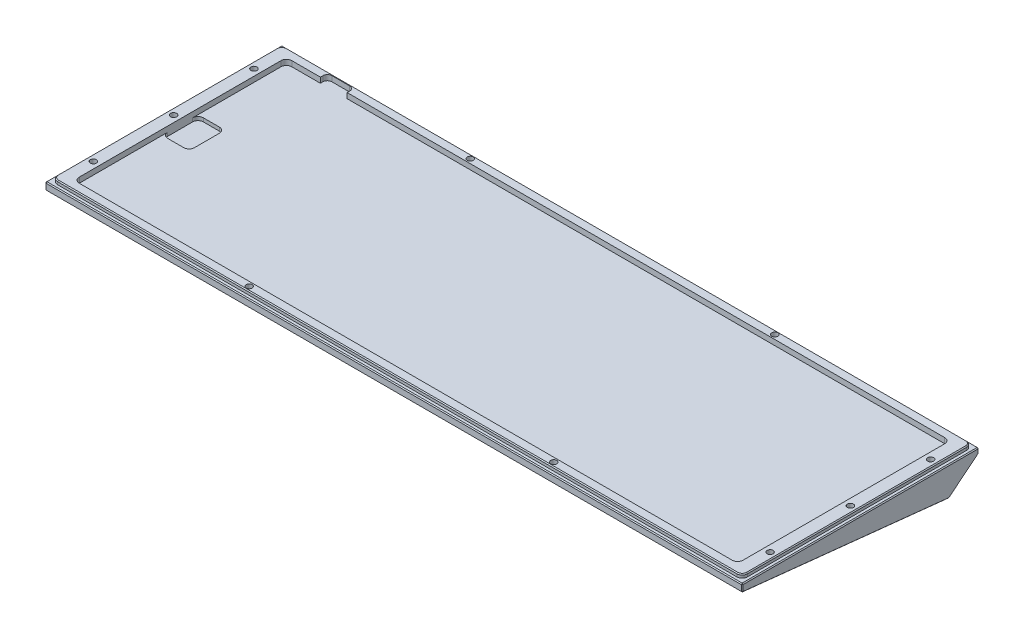
SolidWorks part; units mm, degrees
material "6061-T6 (SS)"
ref_plane "Front Plane" through (0, 0, 0) normal (0, 0, 1) x (1, 0, 0)
ref_plane "Top Plane" through (0, 0, 0) normal (0, 1, 0) x (1, 0, 0)
ref_plane "Right Plane" through (0, 0, 0) normal (1, 0, 0) x (0, 0, -1)
sketch "Sketch1" plane through (0, 0, 0) normal (0, 1, 0) x (1, 0, 0)
  line L1 (0, 0) -> (390.7, 0)
  line L2 (0, 0) -> (0, 132.7)
  line L3 (0, 132.7) -> (390.7, 132.7)
  line L4 (390.7, 0) -> (390.7, 132.7)
  dimension "D1" = 390.7
  dimension "D2" = 132.7
extrude "MainBody" add sketch "Sketch1" along normal blind 18.5
sketch "Sketch2" plane through (0, 18.5, 0) normal (0, 1, 0) x (1, 0, 0)
  line L0 (390.7, 132.7) -> (0, 132.7) construction
  line L1 (2, 130.7) -> (388.7, 130.7)
  line L2 (2, 130.7) -> (2, 2)
  line L3 (2, 2) -> (388.7, 2)
  line L4 (388.7, 130.7) -> (388.7, 2)
  line L5 (0, 132.7) -> (0, 0) construction
  line L7 (0, 132.7) -> (390.7, 132.7)
  line L8 (0, 132.7) -> (0, 0)
  line L9 (0, 0) -> (390.7, 0)
  line L10 (390.7, 132.7) -> (390.7, 0)
  point P4 (195.35, 130.7)
  point P7 (195.35, 132.7)
  point P8 (2, 66.35)
  point P11 (0, 66.35)
  line M5 (0, 132.7) -> (0, 0)
  line M6 (0, 0) -> (390.7, 0)
  line M7 (390.7, 0) -> (390.7, 132.7)
  line M8 (390.7, 132.7) -> (0, 132.7)
  dimension "D1" = 2
  dimension "D2" = 2
extrude "AligmentLip" cut sketch "Sketch2" against normal blind 2 contours L1 L4 L3 L2 M8 M5 M6 M7 region at (195.35, 18.5, -132.2874)
sketch "Sketch3" plane through (0, 0, 0) normal (-1, 0, 0) x (0, 0, 1)
  line L0 (-132.7, 13.5) -> (-116.0289, 0)
  line L1 (-132.7, 16.5) -> (-132.7, 0) construction
  line L2 (-132.7, 0) -> (0, 0) construction
  line L3 (-116.0289, 0) -> (0, 12.1951)
  line L4 (0, 16.5) -> (0, 0) construction
  line L5 (-132.7, 16.5) -> (0, 16.5) construction
  line L7 (-132.7, 16.5) -> (0, 16.5)
  line L8 (-132.7, 16.5) -> (-132.7, 0)
  line L9 (-132.7, 0) -> (0, 0)
  line L10 (0, 16.5) -> (0, 0)
  line M4 (-132.7, 16.5) -> (-132.7, 0)
  line M5 (-132.7, 0) -> (0, 0)
  line M6 (0, 0) -> (0, 16.5)
  dimension "D1" = 6
  dimension "D2" = 135
  dimension "D3" = 3
extrude "TypingAngle" cut sketch "Sketch3" against normal through all contours L0 M4 M5 | L3 M5 M6 region at (0, 4.5, -127.143) region at (0, 4.065, -38.6763)
sketch "Sketch4" plane through (0, 18.5, 0) normal (0, 1, 0) x (1, 0, 0)
  line L0 (2, 130.7) -> (388.7, 130.7) construction
  line L1 (9.35, 125.9) -> (381.35, 125.9)
  line L2 (9.35, 125.9) -> (9.35, 6.8)
  line L3 (9.35, 6.8) -> (381.35, 6.8)
  line L4 (381.35, 125.9) -> (381.35, 6.8)
  line L5 (2, 130.7) -> (2, 2) construction
  point P4 (195.35, 125.9)
  point P7 (195.35, 130.7)
  point P8 (9.35, 66.35)
  point P11 (2, 66.35)
  dimension "D1" = 372
  dimension "D2" = 119.1
extrude "PCBCutout" cut sketch "Sketch4" against normal blind 3
sketch "Sketch8" plane through (0, 18.5, 0) normal (0, 1, 0) x (1, 0, 0)
  line L0 (195.35, 132.7) -> (195.35, 0) construction
  line L1 (390.7, 132.7) -> (0, 132.7) construction
  line L2 (0, 0) -> (390.7, 0) construction
  line L3 (0, 66.35) -> (195.35, 66.35) construction
  line L4 (0, 132.7) -> (0, 0) construction
  line L5 (2, 130.7) -> (388.7, 130.7) construction
  line L6 (2, 2) -> (388.7, 2) construction
  line L7 (2, 130.7) -> (2, 2) construction
  point P11 (110, 128.3)
  point P12 (5.7, 111.35)
  point P13 (5.7, 66.35)
  point P14 (5.7, 21.35)
  point P16 (110, 4.4)
  point P27 (280.7, 4.4)
  point P28 (385, 21.35)
  point P29 (385, 66.35)
  point P30 (385, 111.35)
  point P31 (280.7, 128.3)
  dimension "D1" = 2.4
  dimension "D2" = 2.4
  dimension "D3" = 110
  dimension "D4" = 45
  dimension "D5" = 45
  dimension "D6" = 3.7
hole_wizard "M3 Clearance Hole1" positions "3DSketch7" profile "Sketch10" hole size "M3" standard "ANSI Metric" end condition through all
sketch3d "3DSketch7"
  point P0 (110, 18.5, -128.3)
  point P3 (5.7, 18.5, -111.35)
  point P6 (5.7, 18.5, -66.35)
  point P9 (5.7, 18.5, -21.35)
  point P12 (110, 18.5, -4.4)
  point P15 (280.7, 18.5, -128.3)
  point P18 (280.7, 18.5, -4.4)
  point P21 (385, 18.5, -21.35)
  point P24 (385, 18.5, -66.35)
  point P27 (385, 18.5, -111.35)
sketch "Sketch10" plane through (110, 18.5, -128.3) normal (1, 0, 0) x (0, 0, 1)
  line L0 (0, 0) -> (0, 18.5)
  line L1 (0, 18.5) -> (1.7, 18.5)
  line L2 (1.7, 18.5) -> (1.7, 0)
  line L5 (1.7, 0) -> (0, 0)
  line L11 (0, -6.35) -> (0, 107.95) construction
  dimension "Thru Hole Dia." = 3.4
  dimension "Thru Hole Depth" = 18.5
sketch "Sketch11" plane through (0, 15.5, 0) normal (0, 1, 0) x (1, 0, 0)
  line L0 (195.35, 132.7) -> (195.35, 0) construction
  line L1 (0, 0) -> (390.7, 0) construction
  circle A0 centre (110, 128.3) radius 3.25
  circle A1 centre (5.7, 111.35) radius 3.25
  circle A2 centre (5.7, 66.35) radius 3.25
  circle A3 centre (5.7, 21.35) radius 3.25
  circle A4 centre (110, 4.4) radius 3.25
  circle A5 centre (280.7, 4.4) radius 3.25
  circle A6 centre (385, 21.35) radius 3.25
  circle A7 centre (385, 66.35) radius 3.25
  circle A8 centre (385, 111.35) radius 3.25
  circle A9 centre (280.7, 128.3) radius 3.25
  dimension "D1" = 6.5
extrude "Cut-Extrude2" cut sketch "Sketch11" against normal through all from offset 1 offset against normal yes
sketch "Sketch12" plane through (0, 18.5, 0) normal (0, 1, 0) x (1, 0, 0)
  line L0 (381.35, 125.9) -> (9.35, 125.9) construction
  line L1 (28.4, 125.9) -> (43.4, 125.9)
  line L2 (28.4, 125.9) -> (28.4, 129.85)
  line L3 (28.4, 129.85) -> (43.4, 129.85)
  line L4 (43.4, 125.9) -> (43.4, 129.85)
  line L5 (0, 132.7) -> (0, 0) construction
  line L6 (390.7, 132.7) -> (0, 132.7) construction
  point P6 (35.9, 129.85)
  dimension "D1" = 15
  dimension "D2" = 2.85
  dimension "D3" = 35.9
extrude "Cut-Extrude3" cut sketch "Sketch12" against normal up to surface (3 mm away) up to face at (195.35, 15.5, -66.35)
fillet "Fillet1" radius 2.5 2 edges at (43.4, 17, -129.85) (28.4, 17, -129.85)
sketch "Sketch13" plane through (0, 15.5, 0) normal (0, 1, 0) x (1, 0, 0)
  line L0 (9.35, 125.9) -> (9.35, 6.8) construction
  line L1 (9.35, 76.35) -> (24.35, 76.35)
  line L2 (9.35, 76.35) -> (9.35, 56.35)
  line L3 (9.35, 56.35) -> (24.35, 56.35)
  line L4 (24.35, 76.35) -> (24.35, 56.35)
  line L5 (2, 130.7) -> (2, 2) construction
  point P6 (9.35, 66.35)
  point P9 (2, 66.35)
  dimension "D1" = 15
  dimension "D2" = 20
extrude "Cut-Extrude4" cut sketch "Sketch13" against normal blind 2
fillet "Fillet2" radius 3 12 edges at (381.35, 17, -125.9) (388.7, 17.5, -130.7) (388.7, 17.5, -2) (381.35, 17, -6.8) (9.35, 17, -6.8) (2, 17.5, -2) (9.35, 17, -125.9) (2, 17.5, -130.7) (9.35, 14.5, -56.35) (24.35, 14.5, -56.35) (9.35, 14.5, -76.35) (24.35, 14.5, -76.35)
chamfer "Chamfer1" distance 0.5 angle 45 13 edges at (195.35, 12.1951, 0) (390.7, 15, -132.7) (0, 15, -132.7) (0, 6.75, -124.3644) (390.7, 6.75, -124.3644) (390.7, 6.0976, -58.0144) (390.7, 14.3476, 0) (0, 6.0976, -58.0144) (0, 14.3476, 0) (0, 16.5, -66.35) (195.35, 16.5, 0) (390.7, 16.5, -66.35) (195.35, 16.5, -132.7) first distance on face at (195.35, 14.3476, 0) first distance on face at (195.35, 15, -132.7) first distance on face at (280.7, 12.5687, -131.55) first distance on face at (385, 0.8334, -108.1) first distance on face at (0, 11.739, -76.2858) first distance on face at (390.7, 11.739, -76.2858)
chamfer "Chamfer2" distance 0.5 angle 45 8 edges at (388.7, 18.5, -66.35) (387.8213, 18.5, -129.8213) (387.8213, 18.5, -2.8787) (195.35, 18.5, -130.7) (195.35, 18.5, -2) (2.8787, 18.5, -129.8213) (2.8787, 18.5, -2.8787) (2, 18.5, -66.35)
sketch "Sketch17" plane through (0, 12.0619, -1.2678) normal (0, -0.9945, 0.1045) x (1, 0, 0)
  line L0 (198.1, -60.7253) -> (196.1, -60.7253) construction
  line L1 (198.1, -68.7253) -> (196.1, -68.7253)
  line L2 (198.1, -68.7253) -> (198.1, -52.7253)
  line L3 (198.1, -52.7253) -> (196.1, -52.7253)
  line L4 (196.1, -68.7253) -> (196.1, -52.7253)
  line L5 (202.6, -61.2253) -> (200.6, -61.2253)
  line L6 (202.6, -61.2253) -> (202.6, -48.7253)
  line L7 (202.6, -48.7253) -> (200.6, -48.7253)
  line L8 (200.6, -61.2253) -> (200.6, -48.7253)
  line L9 (193.6, -61.2253) -> (191.6, -61.2253)
  line L10 (193.6, -61.2253) -> (193.6, -53.2253)
  line L11 (193.6, -53.2253) -> (191.6, -53.2253)
  line L12 (191.6, -61.2253) -> (191.6, -53.2253)
  line L13 (190.1, -61.2253) -> (188.1, -61.2253)
  line L14 (190.1, -61.2253) -> (190.1, -53.2253)
  line L15 (190.1, -53.2253) -> (188.1, -53.2253)
  line L16 (188.1, -61.2253) -> (188.1, -53.2253)
  line L17 (186.6, -61.2253) -> (184.6, -61.2253)
  line L18 (186.6, -61.2253) -> (186.6, -53.2253)
  line L19 (186.6, -53.2253) -> (184.6, -53.2253)
  line L20 (184.6, -61.2253) -> (184.6, -53.2253)
  line L25 (202.6, -61.2253) -> (188.1, -61.2253) construction
  line L26 (390.2, -115.3933) -> (0.5, -115.3933) construction
  line L27 (194.1, -64.7253) -> (198.1, -64.7253)
  line L28 (194.1, -62.7253) -> (198.1, -62.7253)
  line L29 (390.7, 1.2747) -> (0, 1.2747) construction
  line L31 (206.1, -53.2253) -> (204.1, -53.2253)
  line L32 (206.1, -53.2253) -> (206.1, -48.7253)
  line L33 (206.1, -48.7253) -> (204.1, -48.7253)
  line L34 (204.1, -53.2253) -> (204.1, -48.7253)
  circle A0 centre (201.6, -63.7253) radius 1
  circle A2 centre (194.1, -63.7253) radius 1
  circle A3 centre (197.1, -67.7253) radius 1
  circle A4 centre (197.1, -53.7253) radius 1
  circle A5 centre (201.6, -60.2253) radius 1
  circle A6 centre (201.6, -49.7253) radius 1
  circle A7 centre (205.1, -52.2253) radius 1
  circle A8 centre (205.1, -49.7253) radius 1
  circle A9 centre (192.6, -60.2253) radius 1
  circle A10 centre (192.6, -54.2253) radius 1
  circle A11 centre (189.1, -60.2253) radius 1
  circle A12 centre (189.1, -54.2253) radius 1
  circle A13 centre (185.6, -60.2253) radius 1
  circle A14 centre (185.6, -54.2253) radius 1
  point P28 (195.35, -61.2253)
  point P29 (201.6, -61.2253)
  point P33 (195.35, -115.3933)
  point P44 (197.1, -68.7253)
  dimension "D12" = 2
  dimension "D13" = 12.5
  dimension "D16" = 2
  dimension "D1" = 16
  dimension "D2" = 2
  dimension "D3" = 0
  dimension "D4" = 2.5
  dimension "D5" = 2.5
  dimension "D6" = 1.5
  dimension "D7" = 1.5
  dimension "D8" = 8
  dimension "D9" = 0.5
  dimension "D10" = 1.5
  dimension "D11" = 2.5
  dimension "D14" = 4.5
  dimension "D15" = 50
  dimension "D17" = 2
  dimension "D18" = 3
  dimension "D19" = 11
extrude "Cut-Extrude5" cut sketch "Sketch17" against normal blind 1 contours A7 | A8 L34 A7 L32 | A8 | A6 | A6 L8 A5 L6 | A5 | A4 | A4 L4 L28 L2 | L28 L4 L27 L2 | A3 L2 L27 L4 | A3 | A2 L27 L4 L28 | A2 | A0 | A9 | A10 L12 A9 L10 | A10 | A12 L16 A11 L14 | A11 | A12 | A14 | A14 L20 A13 L18 | A13 region at (197.1, 4.9827, -68.622) region at (197.1, 5.1793, -66.7509) region at (197.1, 5.4008, -64.6439) region at (195.4722, 5.4008, -64.6439) region at (197.1, 5.935, -59.5616) region at (194.1, 5.4008, -64.6439) region at (197.1, 6.4461, -54.6987) region at (201.6, 5.7666, -61.1631) region at (201.6, 6.3154, -55.9419) region at (201.6, 6.8642, -50.7206) region at (192.6, 5.7666, -61.1631) region at (192.6, 6.0802, -58.1795) region at (192.6, 6.3938, -55.196) region at (189.1, 5.7666, -61.1631) region at (189.1, 6.0802, -58.1795) region at (189.1, 6.3938, -55.196) region at (185.6, 5.7666, -61.1631) region at (185.6, 6.0802, -58.1795) region at (185.6, 6.3938, -55.196) region at (205.1, 6.6029, -53.2069) region at (205.1, 6.7335, -51.9638) region at (205.1, 6.8642, -50.7206) region at (201.6, 5.4008, -64.6439)
